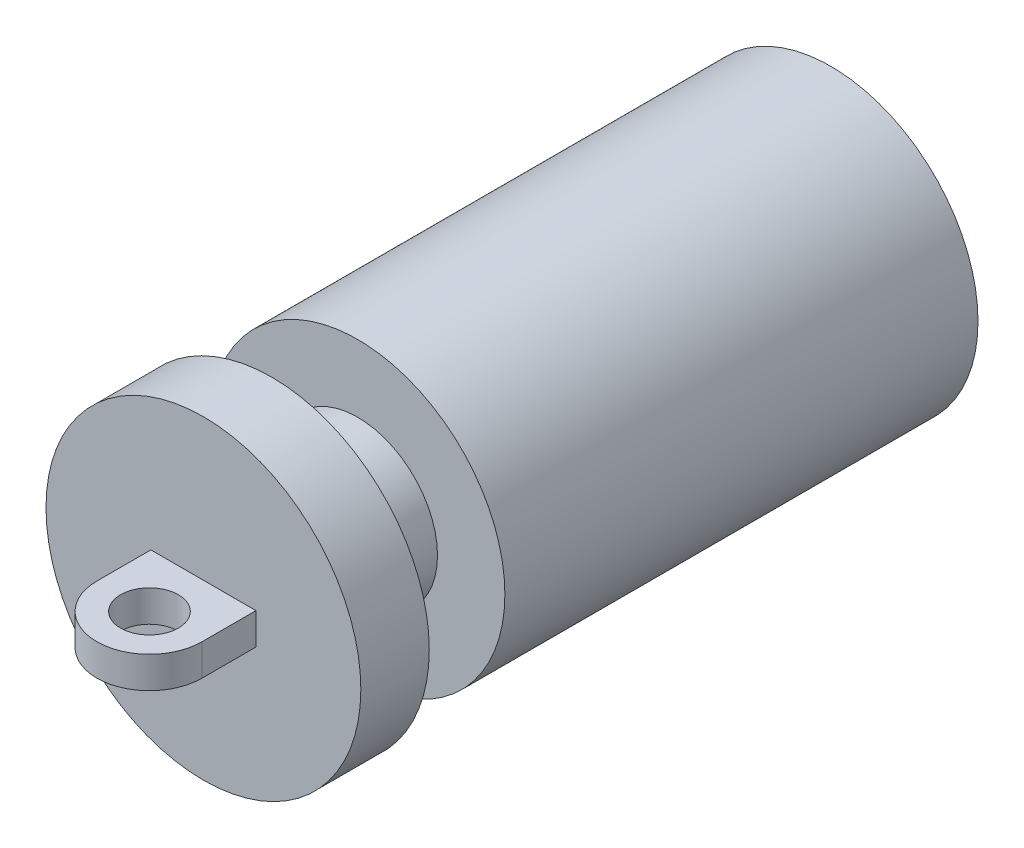
SolidWorks part; units mm, degrees
ref_plane "Front Plane" through (0, 0, 0) normal (0, 0, 1) x (1, 0, 0)
ref_plane "Top Plane" through (0, 0, 0) normal (0, 1, 0) x (1, 0, 0)
ref_plane "Right Plane" through (0, 0, 0) normal (1, 0, 0) x (0, 0, -1)
sketch "Sketch2" plane through (0, 0, 0) normal (0, 0, 1) x (1, 0, 0)
  circle A0 centre (0, 0) radius 15
  dimension "D1" = 30
sketch "Sketch3" plane through (0, 0, 0) normal (1, 0, 0) x (0, 0, -1)
  line L0 (-4.0824, 7.592) -> (4.0824, 7.592)
  line L4 (-10.591, 14.9728) -> (-10.591, 0)
  line L7 (-4.0824, 14.9728) -> (-4.0824, 7.592)
  line L8 (0, 15) -> (0, -15) construction
  line L9 (16.5, 0) -> (-16.5, 0) construction
  line L10 (-10.591, 0) -> (4.0824, 0)
  line L13 (0, 16.5) -> (0, -16.5) construction
  line L16 (-4.0824, 14.9728) -> (-10.591, 14.9728)
  line L19 (4.0824, 7.592) -> (4.0824, 0)
  line L21 (-16.3935, 0) -> (16.347, 0) construction
  point P16 (0, 0)
  point P17 (0, 0)
  point P18 (0, -7.592)
  point P19 (0, 7.592)
  point P21 (0, 0)
  point P23 (0, 0)
revolve "Revolve2" add sketch "Sketch3" angle 360 about L21
sketch "Sketch4" plane through (0, 0, 0) normal (0, 1, 0) x (1, 0, 0)
  line L0 (-5, -15.7238) -> (-5, -10.591)
  line L1 (-14.9728, -10.591) -> (14.9728, -10.591) construction
  line L2 (-5, -10.591) -> (5, -10.591)
  line L3 (5, -10.591) -> (5, -15.7238)
  circle A0 centre (0, -15.7238) radius 2.75
  arc A1 (-5, -15.7238) -> (5, -15.7238) centre (0, -15.7238) ccw
  dimension "D1" = 5.5
  dimension "D2" = 10
extrude "Boss-Extrude1" add sketch "Sketch4" along normal mid plane 3
sketch "Sketch5" plane through (0, 0, -4.0824) normal (0, 0, -1) x (-1, 0, 0)
  circle A0 centre (0, 0) radius 14
  dimension "D1" = 28
extrude "Boss-Extrude2" add sketch "Sketch5" along normal blind 45
